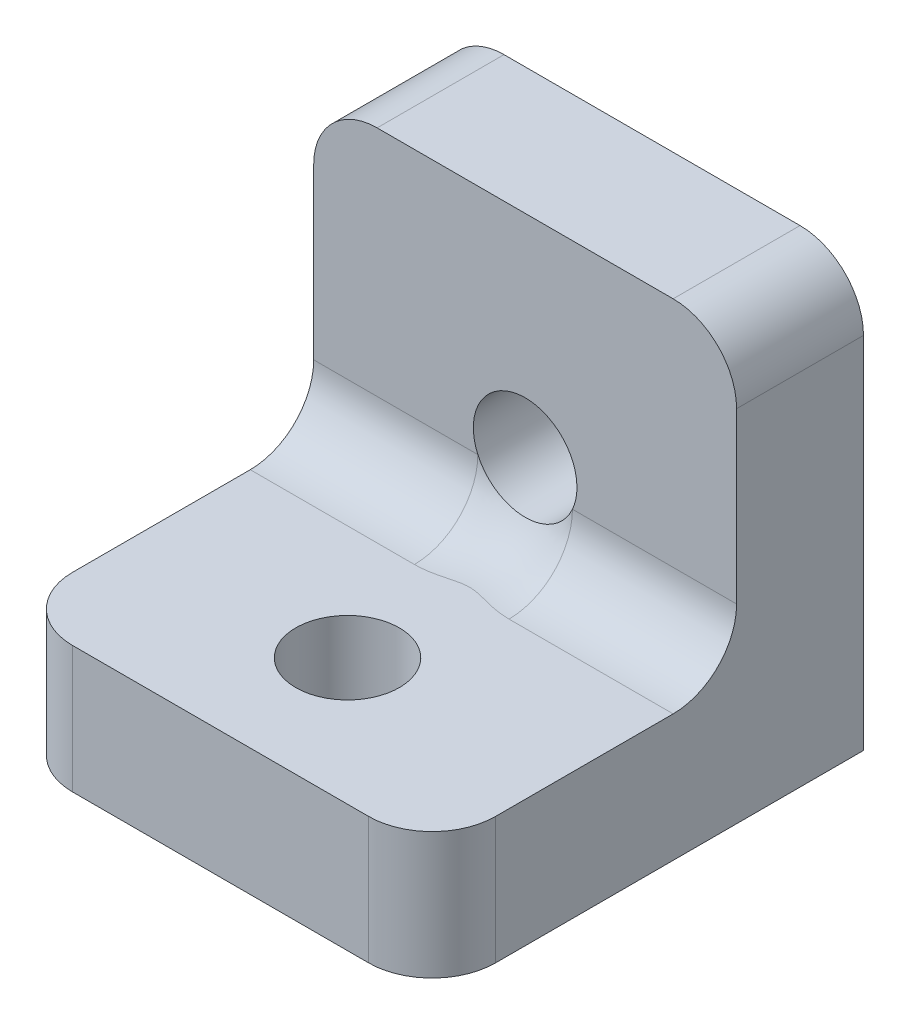
SolidWorks part; units mm, degrees
ref_plane "Front Plane" through (0, 0, 0) normal (0, 0, 1) x (1, 0, 0)
ref_plane "Top Plane" through (0, 0, 0) normal (0, 1, 0) x (1, 0, 0)
ref_plane "Right Plane" through (0, 0, 0) normal (1, 0, 0) x (0, 0, -1)
sketch "Sketch1" plane through (0, 0, 0) normal (0, 0, 1) x (1, 0, 0)
  line L1 (0, 0) -> (20, 0)
  line L2 (0, 0) -> (0, -20)
  line L3 (0, -20) -> (20, -20)
  line L4 (20, 0) -> (20, -20)
  dimension "D1" = 20
  dimension "D2" = 20
extrude "Boss-Extrude1" add sketch "Sketch1" along normal blind 6
sketch "Sketch2" plane through (0, 0, 6) normal (0, 0, 1) x (1, 0, 0)
  line L0 (20, -20) -> (20, 0) construction
  line L1 (0, -20) -> (20, -20)
  line L2 (0, -20) -> (0, -14)
  line L3 (0, -14) -> (20, -14)
  line L4 (20, -20) -> (20, -14)
  dimension "D1" = 6
extrude "Boss-Extrude2" add sketch "Sketch2" along normal blind 14.4
sketch "Sketch3" plane through (0, 0, 6) normal (0, 0, 1) x (1, 0, 0)
  line L0 (20, 0) -> (0, 0) construction
  circle A0 centre (10, -10) radius 2.45
  dimension "D1" = 4.9
  dimension "D2" = 10
extrude "Cut-Extrude1" cut sketch "Sketch3" against normal through all
sketch "Sketch4" plane through (0, -14, 0) normal (0, 1, 0) x (1, 0, 0)
  line L0 (20, -20.4) -> (0, -20.4) construction
  circle A0 centre (10, -14.4) radius 2.45
  dimension "D1" = 4.9
  dimension "D2" = 6
extrude "Cut-Extrude2" cut sketch "Sketch4" against normal through all
fillet "Fillet1" radius 3 4 edges at (0, 0, 3) (20, 0, 3) (20, -17, 20.4) (0, -17, 20.4)
fillet "Fillet2" radius 3 1 edges at (10, -14, 6)
equation "\"滑动-垂直孔\"= 0.6"
equation "\"滑动-水平孔\"= 0.3"
equation "\"松动-垂直孔\"= 0.3"
equation "\"松动-水平孔\"= 0.1"
equation "\"正常-垂直孔\"= 0.15"
equation "\"正常-水平孔\"= 0"
equation "\"紧缩-垂直孔\"= 0"
equation "\"紧缩-水平孔\"= - 0.1"
equation "\"D1@Sketch3\"=\"紧缩-水平孔\"+5"
equation "\"D1@Sketch4\"=\"D1@Sketch3\""
